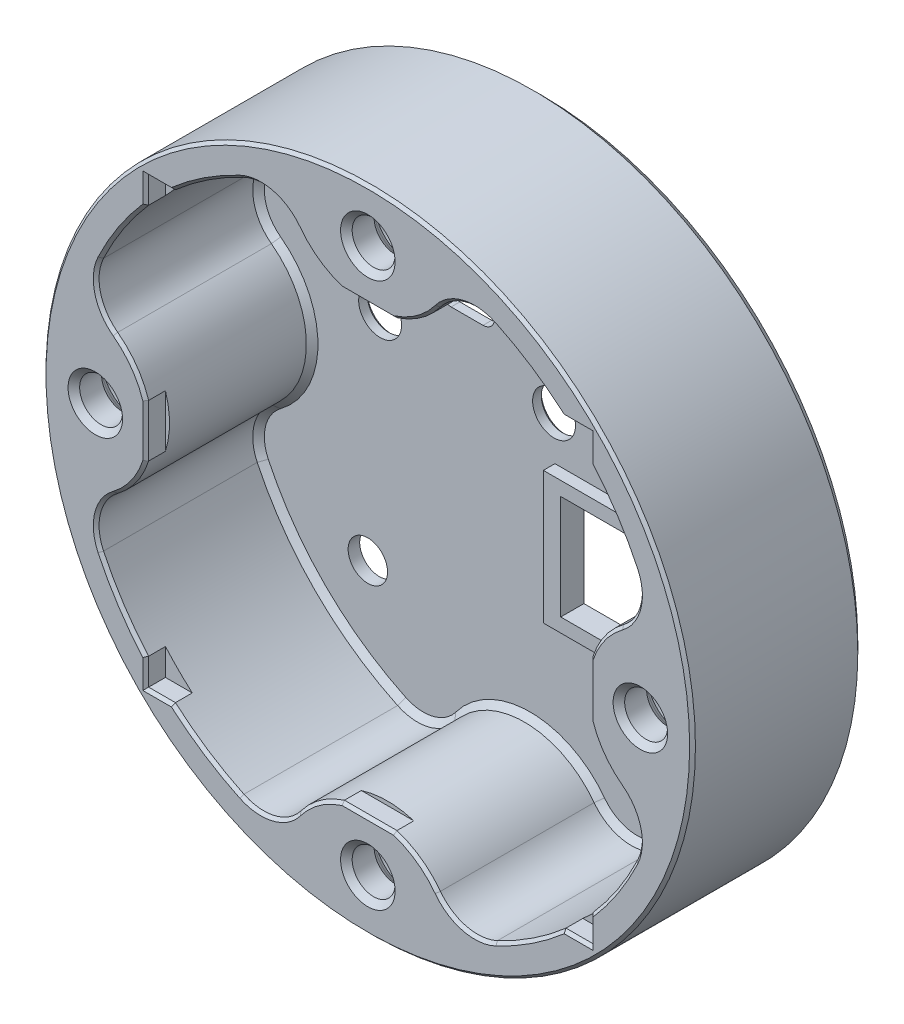
SolidWorks part; units mm, degrees
ref_plane "Front Plane" through (0, 0, 0) normal (0, 0, 1) x (1, 0, 0)
ref_plane "Top Plane" through (0, 0, 0) normal (0, 1, 0) x (1, 0, 0)
ref_plane "Right Plane" through (0, 0, 0) normal (1, 0, 0) x (0, 0, -1)
sketch "Sketch1" plane through (0, 0, 0) normal (0, 0, 1) x (1, 0, 0)
  circle A0 centre (0, 0) radius 28
  dimension "D1" = 56
extrude "Extrude1" add sketch "Sketch1" along normal blind 1
sketch "Sketch2" plane through (0, 0, 1) normal (0, 0, 1) x (1, 0, 0)
  circle A0 centre (0, 0) radius 28
  circle A1 centre (0, 0) radius 28 construction
  circle A2 centre (0, 0) radius 25.5
  dimension "D1" = 2.5
extrude "Extrude2" add sketch "Sketch2" along normal blind 14
sketch "Sketch3" plane through (0, 0, 15) normal (0, 0, 1) x (1, 0, 0)
  line L0 (0, 0) -> (0, 33.2655) construction
  line L1 (0, 0) -> (36.569, 0) construction
  line L2 (24.4428, 7.2664) -> (28, 0)
  line L3 (28, 0) -> (24.4428, -7.2664)
  line L4 (0, -28) -> (-7.2664, -24.4428)
  line L5 (7.2664, -24.4428) -> (0, -28)
  line L6 (-28, 0) -> (-24.4428, 7.2664)
  line L7 (-24.4428, -7.2664) -> (-28, 0)
  line L8 (0, 28) -> (7.2664, 24.4428)
  line L9 (-7.2664, 24.4428) -> (0, 28)
  circle A0 centre (23.5, 0) radius 1.85
  circle A1 centre (0, 0) radius 28 construction
  circle A2 centre (23.5, 0) radius 3.075
  circle A3 centre (0, -23.5) radius 3.075
  circle A4 centre (0, -23.5) radius 1.85
  circle A5 centre (-23.5, 0) radius 3.075
  circle A6 centre (-23.5, 0) radius 1.85
  circle A7 centre (0, 23.5) radius 3.075
  circle A8 centre (0, 23.5) radius 1.85
  arc A9 (24.4428, 7.2664) -> (24.4428, -7.2664) centre (26.3, 0) ccw
  circle A10 centre (0, 0) radius 25.5 construction
  arc A11 (7.2664, -24.4428) -> (-7.2664, -24.4428) centre (0, -26.3) ccw
  arc A12 (-24.4428, -7.2664) -> (-24.4428, 7.2664) centre (-26.3, 0) ccw
  arc A13 (-7.2664, 24.4428) -> (7.2664, 24.4428) centre (0, 26.3) ccw
  point P8 (28, 0)
  circle M12 centre (0, 0) radius 25.5
  dimension "D2" = 3.7
  dimension "D3" = 6.15
  dimension "D5" = 7.5
  dimension "D1" = 4.5
  dimension "D4" = 4
  dimension "D6" = 2.8
  dimension "D7" = 4
extrude "Extrude3" add sketch "Sketch3" against normal up to surface (14 mm away) contours A12 A5 M12 | A13 A7 M12 | A7 A8 M12 | A5 A6 M12 | A3 A4 M12 | A11 A3 M12 | A9 A2 M12 | A2 A0 M12 region at (24.8738, 4.8407, 15) region at (0, 18.9595, 15) region at (25.3913, 1.2127, 15) region at (4.8407, -24.8738, 15) region at (2.8339, 24.4698, 15) region at (0, -25.4203, 15) region at (-18.9595, 0, 15) region at (-22.1818, 2.6896, 15) up to face at (25.5, 0, 1)
sketch "Sketch5" plane through (0, 0, 15) normal (0, 0, 1) x (1, 0, 0)
  line L1 (-19.15, -19.15) -> (19.15, -19.15)
  line L2 (-19.15, -19.15) -> (-19.15, 19.15)
  line L3 (-19.15, 19.15) -> (19.15, 19.15)
  line L4 (19.15, -19.15) -> (19.15, 19.15)
  line L5 (-19.15, -19.15) -> (19.15, 19.15) construction
  line L6 (-19.15, 19.15) -> (19.15, -19.15) construction
  point P0 (0, 0)
  dimension "D1" = 38.3
extrude "Extrude7" cut sketch "Sketch5" against normal blind 1.7
extrude "Extrude4" cut sketch "Sketch" against normal through all contours A6 | A8 | A0 | A4 region at (23.5, 0, 15) region at (0, -23.5, 15) region at (-23.5, 0, 15) region at (0, 23.5, 15)
sketch "Sketch" plane through (0, 0, 15) normal (0, 0, 1) x (1, 0, 0) same geometry as "Sketch3"
extrude "Extrude5" cut sketch "Sketch" along normal offset from surface (12 mm away) 3 from surface contours A5 A6 M12 | A5 M12 | A7 A8 M12 | A7 M12 | A2 A0 M12 | A2 M12 | A3 A4 M12 | A3 M12 region at (25.3913, 1.2127, 15) region at (25.9144, 0, 15) region at (0, 25.9144, 15) region at (2.8339, 24.4698, 15) region at (0, -25.4203, 15) region at (0, -25.9144, 15) region at (-25.9144, 0, 15) region at (-22.1818, 2.6896, 15) up to face at (0, 0, 15) starting at face at (-21.65, 0, 0)
sketch "Sketch" plane through (0, 0, 15) normal (0, 0, 1) x (1, 0, 0) same geometry as "Sketch3"
chamfer "Chamfer1" distance 0.6125 angle 45 8 edges at (3.075, -23.5, 12) (1.85, -23.5, 12) (26.575, 0, 12) (25.35, 0, 12) (-20.425, 0, 12) (-21.65, 0, 12) (3.075, 23.5, 12) (1.85, 23.5, 12)
chamfer "Chamfer2" distance 0.75 angle 45 1 edges at (28, 0, 0)
chamfer "Chamfer3" distance 0.5 angle 45 4 edges at (3.075, -23.5, 0) (-20.425, 0, 0) (3.075, 23.5, 0) (26.575, 0, 0)
fillet "Fillet1" radius 4 8 edges at (-24.4428, 7.2664, 8) (-24.4428, -7.2664, 8) (-7.2664, -24.4428, 8) (7.2664, -24.4428, 8) (24.4428, -7.2664, 8) (24.4428, 7.2664, 8) (-7.2664, 24.4428, 8) (7.2664, 24.4428, 8)
sketch "Sketch4" plane through (0, 0, 1) normal (0, 0, 1) x (1, 0, 0)
  line L0 (-5.4418, 5.0365) -> (2.0582, 5.0365) construction
  line L5 (-7.8168, 8.5365) -> (-3.0668, 8.5365)
  line L6 (-7.8168, 8.5365) -> (-7.8168, 18.5365)
  line L7 (-7.8168, 18.5365) -> (-3.0668, 18.5365)
  line L8 (-3.0668, 8.5365) -> (-3.0668, 18.5365)
  line L9 (-7.8168, 8.5365) -> (-3.0668, 18.5365) construction
  line L10 (-7.8168, 18.5365) -> (-3.0668, 8.5365) construction
  line L11 (-5.4418, 13.5365) -> (-5.4418, 8.5365) construction
  line L13 (-14, -14) -> (14, -14) construction
  line L14 (-14, -14) -> (-14, 14) construction
  line L15 (-14, 14) -> (14, 14) construction
  line L16 (14, -14) -> (14, 14) construction
  line L17 (-14, -14) -> (14, 14) construction
  line L18 (-14, 14) -> (14, -14) construction
  line L19 (3.6347, -8.8926) -> (17.6347, -8.8926)
  line L20 (3.6347, -8.8926) -> (3.6347, 0.1074)
  line L21 (3.6347, 0.1074) -> (17.6347, 0.1074)
  line L22 (17.6347, -8.8926) -> (17.6347, 0.1074)
  line L23 (3.6347, -8.8926) -> (17.6347, 0.1074) construction
  line L24 (3.6347, 0.1074) -> (17.6347, -8.8926) construction
  circle A0 centre (2.0582, 5.0365) radius 1.85
  circle A1 centre (-12.9418, 5.0365) radius 1.85
  circle A2 centre (14, 14) radius 1.7
  circle A3 centre (-14, 14) radius 1.7
  circle A4 centre (-14, -14) radius 1.7
  circle A5 centre (14, -14) radius 1.7
  point P0 (-5.4418, 13.5365)
  point P7 (0, 0)
  point P22 (10.6347, -4.3926)
  point P23 (10.6347, -4.3926)
  dimension "D3" = 3.7
  dimension "D7" = 3.4
  dimension "D1" = 4.75
  dimension "D2" = 10
  dimension "D4" = 15
  dimension "D5" = 8.5
  dimension "D6" = 28
  dimension "D8" = 14
  dimension "D9" = 9
extrude "Extrude6" cut sketch "Sketch4" against normal blind 10 contours A3 | A1 | A4 | A0 | L5 L8 L7 L6 | A2 | A5 region at (-5.4418, 13.5365, 1) region at (2.0582, 5.0365, 1) region at (-12.9418, 5.0365, 1) region at (14, 14, 1) region at (-14, 14, 1) region at (-14, -14, 1) region at (14, -14, 1)
fillet "Fillet2" radius 1 4 edges at (-3.0668, 8.5365, 0.5) (-7.8168, 8.5365, 0.5) (-7.8168, 18.5365, 0.5) (-3.0668, 18.5365, 0.5)
chamfer "Chamfer4" distance 0.5 angle 45 16 edges at (18.0312, -18.0312, 1) (8.2538, -23.3059, 1) (23.3059, -8.2538, 1) (0, -18.8, 1) (18.8, 0, 1) (-8.2538, -23.3059, 1) (23.3059, 8.2538, 1) (-18.0312, -18.0312, 1) (18.0312, 18.0312, 1) (-23.3059, -8.2538, 1) (8.2538, 23.3059, 1) (-18.8, 0, 1) (0, 18.8, 1) (-23.3059, 8.2538, 1) (-8.2538, 23.3059, 1) (-18.0312, 18.0312, 1)
chamfer "Chamfer5" distance 0.25 angle 45 47 edges at (28, 0, 15) (-11.0918, 5.0365, 0) (-7.8168, 13.5365, 0) (-7.5239, 8.8294, 0) (-7.5239, 18.2437, 0) (-5.4418, 8.5365, 0) (-5.4418, 18.5365, 0) (-3.3597, 8.8294, 0) (-3.3597, 18.2437, 0) (-3.0668, 13.5365, 0) (3.9082, 5.0365, 0) (20.1885, 4.3473, 15) (23.3059, 8.2538, 15) (21.2994, 14.0209, 15) (19.15, 17.9941, 15) (17.9941, 19.15, 15) (14.0209, 21.2994, 15) (8.2538, 23.3059, 15) (4.3473, 20.1885, 15) (0, 19.15, 15) (-4.3473, 20.1885, 15) (-8.2538, 23.3059, 15) (-14.0209, 21.2994, 15) (-17.9941, 19.15, 15) (-19.15, 17.9941, 15) (-21.2994, 14.0209, 15) (-23.3059, 8.2538, 15) (-20.1885, 4.3473, 15) (-19.15, 0, 15) (-20.1885, -4.3473, 15) (-23.3059, -8.2538, 15) (-21.2994, -14.0209, 15) (-19.15, -17.9941, 15) (-17.9941, -19.15, 15) (-14.0209, -21.2994, 15) (-8.2538, -23.3059, 15) (-4.3473, -20.1885, 15) (0, -19.15, 15) (4.3473, -20.1885, 15) (8.2538, -23.3059, 15) (14.0209, -21.2994, 15) (17.9941, -19.15, 15) (19.15, -17.9941, 15) (21.2994, -14.0209, 15) (23.3059, -8.2538, 15) (20.1885, -4.3473, 15) (19.15, 0, 15)
chamfer "Chamfer6" distance 0.5 angle 45 4 edges at (-21.65, 0, 15) (1.85, 23.5, 15) (1.85, -23.5, 15) (25.35, 0, 15) tangent propagation no
extrude "Extrude8" cut sketch "Sketch" against normal through all contours L19 L22 L21 L20 region at (10.6347, -4.3926, 1)
sketch "Sketch" plane through (0, 0, 1) normal (0, 0, 1) x (1, 0, 0) same geometry as "Sketch4"
sketch "Sketch6" plane through (0, 0, 1) normal (0, 0, 1) x (1, 0, 0)
  line L1 (3.6347, 0.1074) -> (17.6347, 0.1074)
  line L2 (3.6347, 0.1074) -> (3.6347, -8.8926)
  line L3 (3.6347, -8.8926) -> (17.6347, -8.8926)
  line L4 (17.6347, 0.1074) -> (17.6347, -8.8926)
  line L5 (2.1347, 1.3074) -> (19.1347, 1.3074)
  line L6 (2.1347, 1.3074) -> (2.1347, -10.0926)
  line L7 (2.1347, -10.0926) -> (19.1347, -10.0926)
  line L8 (19.1347, 1.3074) -> (19.1347, -10.0926)
  point P10 (19.0997, -11.9329)
  dimension "D1" = 1.5
  dimension "D2" = 1.2
  dimension "D3" = 1.5
  dimension "D4" = 1.2
extrude "Extrude9" add sketch "Sketch6" along normal blind 1
